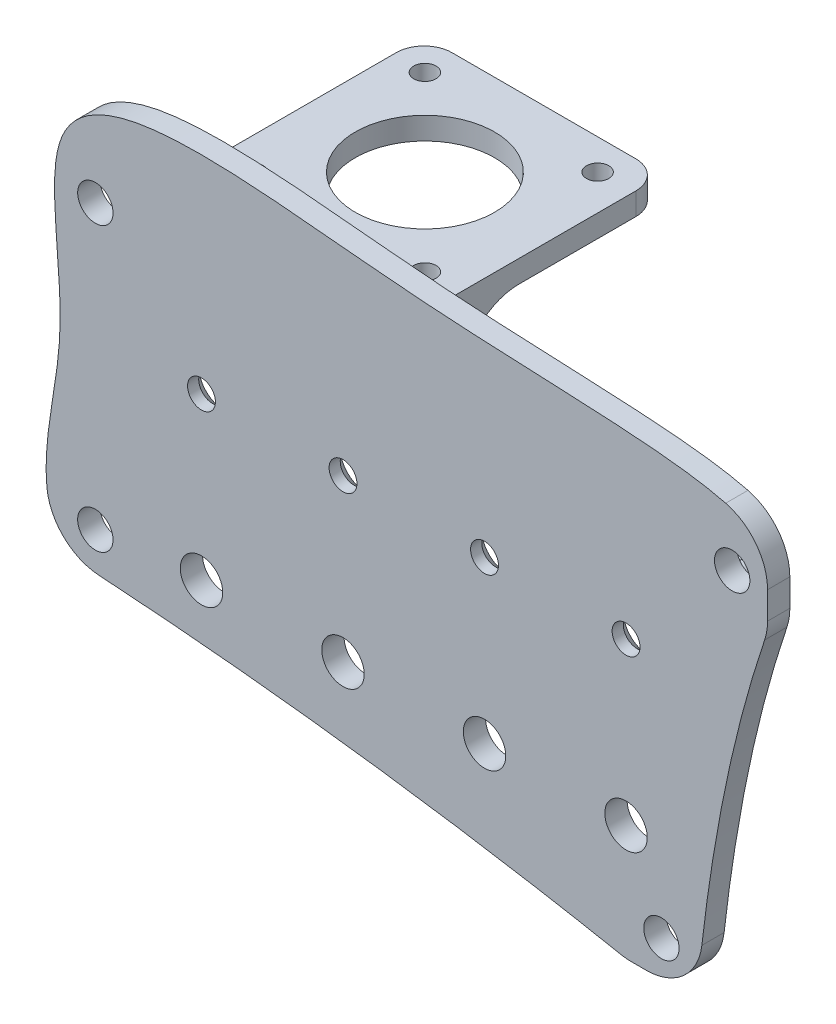
SolidWorks part; units mm, degrees
ref_plane "Front Plane" through (0, 0, 0) normal (0, 0, 1) x (1, 0, 0)
ref_plane "Top Plane" through (0, 0, 0) normal (0, 1, 0) x (1, 0, 0)
ref_plane "Right Plane" through (0, 0, 0) normal (1, 0, 0) x (0, 0, -1)
sketch "Sketch1" plane through (0, 0, 0) normal (0, 0, 1) x (1, 0, 0)
  line L0 (-50.8, -31.75) -> (50.8, -31.75) construction
  line L1 (50.8, -31.75) -> (38.1, -31.75)
  line L2 (50.8, -31.75) -> (50.8, -44.45)
  line L3 (50.8, -44.45) -> (38.1, -44.45)
  line L4 (38.1, -31.75) -> (38.1, -44.45)
  line L5 (-50.8, -19.05) -> (-63.5, -19.05)
  line L6 (63.5, 31.75) -> (50.8, 31.75)
  line L7 (63.5, 31.75) -> (63.5, 19.05)
  line L8 (63.5, 19.05) -> (50.8, 19.05)
  line L9 (50.8, 31.75) -> (50.8, 19.05)
  line L10 (-50.8, 31.75) -> (-63.5, 31.75)
  line L11 (-50.8, 31.75) -> (-50.8, 19.05)
  line L12 (-50.8, 19.05) -> (-63.5, 19.05)
  line L13 (-63.5, 31.75) -> (-63.5, 19.05)
  line L14 (-50.8, -19.05) -> (-50.8, -31.75)
  line L15 (-50.8, -31.75) -> (-63.5, -31.75)
  line L16 (-63.5, -19.05) -> (-63.5, -31.75)
  circle A6 centre (57.15, 25.4) radius 3.175
  circle A7 centre (44.45, -38.1) radius 3.175
  circle A8 centre (44.45, -38.1) radius 3.175 construction
  circle A10 centre (-57.15, -25.4) radius 3.175
  circle A11 centre (-57.15, -25.4) radius 3.175 construction
  circle A12 centre (-57.15, 25.4) radius 3.175
  spline S0 degree 2 poles (-63.5, -31.75) (-12.2595, -34.5619) (38.1, -44.45) knots 0 0 0 1 1 1
  spline S1 degree 2 poles (63.5, 19.05) (54.0502, -8.2327) (50.8, -44.45) knots 0 0 0 1 1 1
  spline S2 degree 3 poles (63.5, 31.75) (56.2648, 38.7509) (1.0243, 36.1193) (-71.9519, 50.0507) (-59.8226, -0.958) (-68.847, -20.4884) (-63.5, -31.75) knots 0 0 0 0 0.33344 0.666881 0.820162 1 1 1 1
  point P21 (38.1, -38.1)
  point P26 (-63.5, -25.4)
  point P36 (0, 0)
  dimension "D7" = 6.35
  dimension "D8" = 6.35
  dimension "D12" = 6.35
  dimension "D13" = 6.35
  dimension "D1" = 12.7
  dimension "D2" = 12.7
  dimension "D3" = 12.7
  dimension "D4" = 12.7
  dimension "D5" = 12.7
  dimension "D6" = 12.7
  dimension "D9" = 12.7
  dimension "D10" = 12.7
extrude "Boss-Extrude1" add sketch "Sketch1" along normal blind 4 contours L10 L13 L12 L11 A12 | L5 L16 L15 L14 A10 | L1 L4 L3 L2 A7 | L6 L9 L8 L7 A6 | L6 S2 L10 L11 L12 L13 L16 L5 L14 L15 S0 L4 L1 L2 S1 L8 L9 region at (50.6204, -38.1, 0) region at (-57.15, 31.5704, 0) region at (-63.3204, -25.4, 0) region at (-2.0522, 1.6662, 0) region at (57.15, 19.2296, 0)
fillet "Fillet1" radius 10 5 edges at (-63.5, -31.75, 2) (38.1, -44.45, 2) (50.8, -44.45, 2) (63.5, 19.05, 2) (63.5, 31.75, 2)
sketch "Sketch2" plane through (0, 0, 0) normal (0, 0, -1) x (-1, 0, 0)
  line L0 (50.8, -23.75) -> (-50.8, -23.75) construction
  line L1 (-50.8, -31.75) -> (-50.8, 31.75) construction
  line L2 (50.8, 31.75) -> (50.8, -31.75) construction
  line L3 (-50.8, -31.75) -> (50.8, -31.75) construction
  line L4 (56.7058, 5.22) -> (-38.1, 5.22) construction
  circle A0 centre (-38.1, -23.75) radius 3.81
  circle A1 centre (-12.7, -23.75) radius 3.81
  circle A2 centre (12.7, -23.75) radius 3.81
  circle A3 centre (38.1, -23.75) radius 3.81
  circle A4 centre (-38.1, 5.22) radius 2.5
  circle A5 centre (-12.7, 5.22) radius 2.5
  circle A6 centre (12.7, 5.22) radius 2.5
  circle A7 centre (38.1, 5.22) radius 2.5
  point P3 (0, -23.75)
  dimension "D2" = 7.62
  dimension "D5" = 5
  dimension "D1" = 8
  dimension "D4" = 38.1
  dimension "D6" = 28.97
  dimension "D3" = 4
  dimension "D7" = 4
extrude "Cut-Extrude1" cut sketch "Sketch2" against normal blind 4
chamfer "Chamfer1" distance 2 angle 45 4 edges at (35.6, 5.22, 0) (10.2, 5.22, 0) (-15.2, 5.22, 0) (-40.6, 5.22, 0)
sketch "Sketch3" plane through (0, 0, 0) normal (0, 0, -1) x (-1, 0, 0)
  line L0 (-47.1417, 16.2739) -> (-45.6185, 14.7507)
  line L1 (-45.6185, 14.7507) -> (-11.4219, 14.7507)
  line L2 (-11.4219, 14.7507) -> (-9.2136, 16.959)
  line L3 (-9.2136, 16.959) -> (1.2442, 16.959)
  line L4 (-49.2631, 14.1526) -> (-46.8612, 11.7507)
  line L5 (-46.8612, 11.7507) -> (-10.1793, 11.7507)
  line L6 (-10.1793, 11.7507) -> (-7.971, 13.959)
  line L7 (-7.971, 13.959) -> (1.2442, 13.959)
  arc A0 (-47.1417, 16.2739) -> (-49.2631, 14.1526) centre (-48.2024, 15.2132) ccw
  arc A1 (1.2442, 16.959) -> (1.2442, 13.959) centre (1.2442, 15.459) cw
  point P4 (-47.1417, 16.2739)
  dimension "D1" = 3
extrude "Boss-Extrude2" add sketch "Sketch3" along normal blind 10
sketch "Sketch4" plane through (0, 0, 0) normal (0, 0, -1) x (-1, 0, 0)
  line L0 (-47.1417, 16.2739) -> (-42.4698, 20.9458)
  line L1 (-45.6185, 14.7507) -> (-47.1417, 16.2739) construction
  line L2 (-42.4698, 20.9458) -> (-13.2005, 20.9458)
  line L3 (-13.2005, 20.9458) -> (-9.2136, 16.959)
  line L4 (-47.1417, 16.2739) -> (-45.6185, 14.7507)
  line L5 (-11.4219, 14.7507) -> (-45.6185, 14.7507) construction
  line L6 (-45.6185, 14.7507) -> (-11.4219, 14.7507)
  line L7 (-11.4219, 14.7507) -> (-9.2136, 16.959)
  arc A0 (-47.1417, 16.2739) -> (-49.2631, 14.1526) centre (-48.2024, 15.2132) ccw construction
  circle A1 centre (-42.5284, 17.5529) radius 1.25
  circle A2 centre (-14.6011, 17.5529) radius 1.25
  dimension "D1" = 2.5
  dimension "D2" = 2.5
extrude "Boss-Extrude3" add sketch "Sketch4" along normal blind 6
sketch "Sketch5" plane through (0, 0, 0) normal (0, 0, -1) x (-1, 0, 0)
  line L0 (-50.8, 31.75) -> (50.8, 31.75) construction
  line L1 (47.15, 31.75) -> (4.15, 31.75)
  line L2 (47.15, 31.75) -> (47.15, 27.75)
  line L3 (47.15, 27.75) -> (4.15, 27.75)
  line L4 (4.15, 31.75) -> (4.15, 27.75)
  circle A0 centre (57.15, 25.4) radius 3.175 construction
  dimension "D1" = 10
  dimension "D2" = 43
  dimension "D3" = 4
extrude "Boss-Extrude4" add sketch "Sketch5" along normal blind 45
sketch "Sketch6" plane through (0, 27.75, 0) normal (0, -1, 0) x (-1, 0, 0)
  circle A0 centre (26, 24) radius 12.5
  circle A1 centre (10.5, 39.5) radius 2
  circle A2 centre (10.5, 39.5) radius 1.5 construction
  circle A3 centre (41.5, 39.5) radius 2
  circle A4 centre (41.5, 8.5) radius 2
  circle A5 centre (10.5, 8.5) radius 2
  point P15 (0, 0)
  point P16 (0, 0)
  dimension "D1" = 25
  dimension "D2" = 4
  dimension "D3" = 4
  dimension "D4" = 4
  dimension "D5" = 4
extrude "Cut-Extrude2" cut sketch "Sketch6" against normal through all
sketch "Sketch7" plane through (-47.15, 0, 0) normal (-1, 0, 0) x (0, 0, 1)
  line L0 (-14.4939, 27.75) -> (0, 11.1992)
  line L1 (-45, 27.75) -> (0, 27.75) construction
  line L2 (-14.4939, 27.75) -> (0, 27.75)
  line L3 (0, 27.75) -> (0, 11.1992)
  line L4 (0, 42.4073) -> (0, -23.1253) construction
  dimension "D1" = 22
extrude "Boss-Extrude5" add sketch "Sketch7" against normal blind 2
pattern_linear "LPattern1" count 2 spacing 41 along (1, 0, 0) of "Boss-Extrude5"
fillet "Fillet2" radius 10 4 edges at (-5.15, 11.1992, 0) (-46.15, 11.1992, 0) (-46.15, 27.75, -14.4939) (-5.15, 27.75, -14.4939)
fillet "Fillet3" radius 5 2 edges at (-4.15, 29.75, -45) (-47.15, 29.75, -45)
